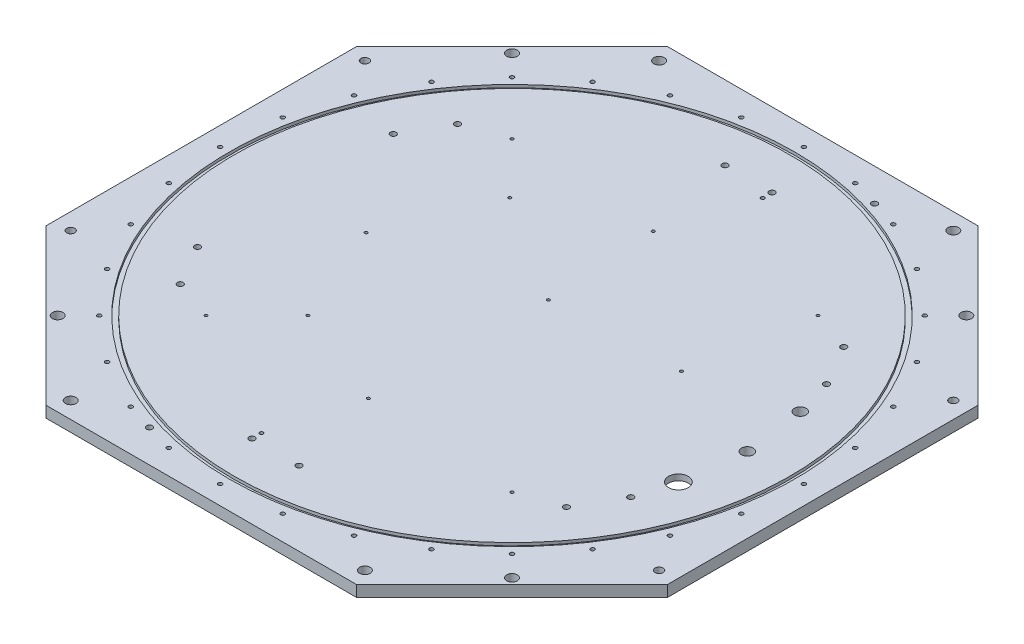
SolidWorks part; units mm, degrees
material "AISI 304"
ref_plane "Front" through (0, 0, 0) normal (0, 0, 1) x (1, 0, 0)
ref_plane "Top" through (0, 0, 0) normal (0, 1, 0) x (1, 0, 0)
ref_plane "Right" through (0, 0, 0) normal (1, 0, 0) x (0, 0, -1)
ref_axis "Axis1" through (0, -5.2388, 0) along (0, 1, 0)
sketch "Sketch1" plane through (0, 0, 0) normal (0, 1, 0) x (1, 0, 0)
  line L0 (-131.9798, 264) -> (131.9798, 264)
  line L1 (131.9798, 264) -> (264, 131.9798)
  line L2 (264, 131.9798) -> (264, -131.9798)
  line L3 (264, 0) -> (0, 0) construction
  line L4 (0, 0) -> (0, 264) construction
  line L5 (131.9798, -264) -> (264, -131.9798)
  line L6 (-131.9798, -264) -> (131.9798, -264)
  line L7 (-131.9798, -264) -> (-264, -131.9798)
  line L8 (-264, 131.9798) -> (-264, -131.9798)
  line L9 (-131.9798, 264) -> (-264, 131.9798)
  point P12 (0, -264)
  point P21 (0, 0)
  dimension "D1" = 528
  dimension "D2" = 280
extrude "Base Plate Profile" add sketch "Sketch1" along normal mid plane 9.525
hole_wizard "M3 Clearance Hole - For Cylinder" positions "Sketch2" profile "Sketch3" hole size "M3" standard "ANSI Metric" end condition up to next
sketch "Sketch2" plane through (0, 4.7625, 0) normal (0, 1, 0) x (1, 0, 0)
  line L0 (-248, 0) -> (248, 0) construction
  point P0 (248, 0)
  point P6 (243.2347, -48.3824)
  point P7 (229.1221, -94.9055)
  point P8 (206.2045, -137.7814)
  point P9 (175.3625, -175.3625)
  point P10 (137.7814, -206.2045)
  point P11 (94.9055, -229.1221)
  point P12 (48.3824, -243.2347)
  point P13 (0, -248)
  point P14 (-48.3824, -243.2347)
  point P15 (-94.9055, -229.1221)
  point P16 (-137.7814, -206.2045)
  point P17 (-175.3625, -175.3625)
  point P18 (-206.2045, -137.7814)
  point P19 (-229.1221, -94.9055)
  point P20 (-243.2347, -48.3824)
  point P21 (-248, 0)
  point P22 (-243.2347, 48.3824)
  point P23 (-229.1221, 94.9055)
  point P24 (-206.2045, 137.7814)
  point P25 (-175.3625, 175.3625)
  point P26 (-137.7814, 206.2045)
  point P27 (-94.9055, 229.1221)
  point P28 (-48.3824, 243.2347)
  point P29 (0, 248)
  point P30 (48.3824, 243.2347)
  point P31 (94.9055, 229.1221)
  point P32 (137.7814, 206.2045)
  point P33 (175.3625, 175.3625)
  point P34 (206.2045, 137.7814)
  point P35 (229.1221, 94.9055)
  point P36 (243.2347, 48.3824)
  dimension "D2" = 496
  dimension "D1" = 32
sketch "Sketch3" plane through (248, 4.7625, 0) normal (1, 0, 0) x (0, 0, 1)
  line L0 (0, 0) -> (0, 9.525)
  line L1 (0, 9.525) -> (1.7, 9.525)
  line L2 (1.7, 9.525) -> (1.7, 0)
  line L5 (1.7, 0) -> (0, 0)
  line L11 (0, -6.35) -> (0, 107.95) construction
  dimension "Thru Hole Dia." = 3.4
  dimension "Thru Hole Depth" = 9.525
hole_wizard "M6x1 Tapped Hole - For Support Pillars" positions "Sketch10" profile "Sketch11" tap size "M6x1.0" standard "ANSI Metric"
sketch "Sketch10" plane through (0, 4.7625, 0) normal (0, 1, 0) x (1, 0, 0)
  line L0 (-20, 201) -> (0, 201) construction
  line L1 (0, 201) -> (20, 201) construction
  line L6 (0, 0) -> (0, 201) construction
  line L7 (-20, -201) -> (20, -201) construction
  line L9 (0, -201) -> (0, 0) construction
  point P0 (-20, 201)
  point P2 (20, 201)
  point P39 (164.0711, 117.8205)
  point P40 (184.0711, 83.1795)
  point P41 (184.0711, -83.1795)
  point P42 (164.0711, -117.8205)
  point P43 (20, -201)
  point P44 (-20, -201)
  point P45 (-164.0711, -117.8205)
  point P46 (-184.0711, -83.1795)
  point P47 (-184.0711, 83.1795)
  point P48 (-164.0711, 117.8205)
  dimension "D1" = 40
  dimension "D2" = 6
  dimension "D3" = 201
cosmetic thread "Hole Thread1" parameters "D1"=6, "D2"=6
cosmetic thread "Hole Thread2" parameters "D1"=6, "D2"=6
cosmetic thread "Hole Thread3" parameters "D1"=6, "D2"=6
cosmetic thread "Hole Thread4" parameters "D1"=6, "D2"=6
cosmetic thread "Hole Thread5" parameters "D1"=6, "D2"=6
cosmetic thread "Hole Thread6" parameters "D1"=6, "D2"=6
cosmetic thread "Hole Thread7" parameters "D1"=6, "D2"=6
cosmetic thread "Hole Thread8" parameters "D1"=6, "D2"=6
cosmetic thread "Hole Thread9" parameters "D1"=6, "D2"=6
cosmetic thread "Hole Thread10" parameters "D1"=6, "D2"=6
cosmetic thread "Hole Thread11" parameters "D1"=6, "D2"=6
cosmetic thread "Hole Thread12" parameters "D1"=6, "D2"=6
sketch "Sketch11" plane through (-20, 4.7625, -201) normal (1, 0, 0) x (0, 0, 1)
  line L0 (0, 0) -> (0, 7.5022)
  line L1 (0, 7.5022) -> (2.5, 6)
  line L2 (2.5, 6) -> (2.5, 0)
  line L5 (2.5, 0) -> (0, 0)
  line L10 (0, 7.5022) -> (-2.5, 6) construction
  line L11 (0, -6.35) -> (0, 107.95) construction
  dimension "Tap Drill Dia." = 5
  dimension "Tap Drill Depth" = 6
  dimension "Drill Angle" = 118
hole_wizard "Ø3.0mm Dowel Hole - For Support Pillars" positions "Sketch12" profile "Sketch13" hole size "Ø3.0" standard "ANSI Metric"
sketch "Sketch12" plane through (0, 4.7625, 0) normal (0, 1, 0) x (1, 0, 0)
  line L1 (20, 193) -> (20, 201) construction
  line L3 (-20, -201) -> (-20, -193) construction
  point P0 (20, 193)
  point P2 (-20, -193)
  dimension "D1" = 8
sketch "Sketch13" plane through (20, 4.7625, -193) normal (1, 0, 0) x (0, 0, 1)
  line L0 (0, 0) -> (0, 6.9013)
  line L1 (0, 6.9013) -> (1.5, 6)
  line L2 (1.5, 6) -> (1.5, 0)
  line L5 (1.5, 0) -> (0, 0)
  line L10 (0, 6.9013) -> (-1.5, 6) construction
  line L11 (0, -6.35) -> (0, 107.95) construction
  dimension "Hole Dia." = 3
  dimension "Hole Depth" = 6
  dimension "Drill Angle" = 118
hole_wizard "M3x0.5 Tapped Hole - For PCB Standoffs" positions "Sketch14" profile "Sketch15" tap size "M3x0.5" standard "ANSI Metric"
sketch "Sketch14" plane through (0, 4.7625, 0) normal (0, 1, 0) x (1, 0, 0)
  line L13 (-150, -150) -> (150, -150) construction
  line L14 (-150, -150) -> (-150, 150) construction
  line L15 (-150, 150) -> (150, 150) construction
  line L16 (150, -150) -> (150, 150) construction
  line L17 (-150, -150) -> (150, 150) construction
  line L18 (-150, 150) -> (150, -150) construction
  point P133 (-130, -130)
  point P136 (130, -130)
  point P138 (130, 130)
  point P140 (-130, 130)
  point P143 (-86.8, -86.7)
  point P145 (0, -122)
  point P149 (-123, -1)
  point P152 (-87.7, 85.8)
  point P154 (4, 27)
  point P157 (-2, 122)
  point P159 (113, 31)
  dimension "D1" = 300
  dimension "D3" = 63.2
  dimension "D4" = 63.3
  dimension "D5" = 28
  dimension "D2" = 20
  dimension "D6" = 27
  dimension "D7" = 149
  dimension "D8" = 235.8
  dimension "D9" = 62.3
  dimension "D10" = 154
  dimension "D11" = 177
  dimension "D12" = 148
  dimension "D13" = 272
  dimension "D14" = 181
  dimension "D15" = 263
sketch "Sketch15" plane through (113, 4.7625, -31) normal (1, 0, 0) x (0, 0, 1)
  line L0 (0, 0) -> (0, 7.2511)
  line L1 (0, 7.2511) -> (1.25, 6.5)
  line L2 (1.25, 6.5) -> (1.25, 0)
  line L5 (1.25, 0) -> (0, 0)
  line L10 (0, 7.2511) -> (-1.25, 6.5) construction
  line L11 (0, -6.35) -> (0, 107.95) construction
  dimension "Tap Drill Dia." = 2.5
  dimension "Tap Drill Depth" = 6.5
  dimension "Drill Angle" = 118
cosmetic thread "Hole Thread13" parameters "D1"=5, "D2"=3
cosmetic thread "Hole Thread14" parameters "D1"=5, "D2"=3
cosmetic thread "Hole Thread15" parameters "D1"=5, "D2"=3
cosmetic thread "Hole Thread16" parameters "D1"=5, "D2"=3
cosmetic thread "Hole Thread17" parameters "D1"=5, "D2"=3
cosmetic thread "Hole Thread18" parameters "D1"=5, "D2"=3
cosmetic thread "Hole Thread19" parameters "D1"=5, "D2"=3
cosmetic thread "Hole Thread20" parameters "D1"=5, "D2"=3
cosmetic thread "Hole Thread21" parameters "D1"=5, "D2"=3
cosmetic thread "Hole Thread22" parameters "D1"=5, "D2"=3
cosmetic thread "Hole Thread23" parameters "D1"=5, "D2"=3
sketch "PCB Size Outline" plane through (0, -4.7625, 0) normal (0, -1, 0) x (1, 0, 0)
  line L1 (-150, -150) -> (150, -150)
  line L2 (-150, -150) -> (-150, 150)
  line L3 (-150, 150) -> (150, 150)
  line L4 (150, -150) -> (150, 150)
  line L5 (-150, -150) -> (150, 150) construction
  line L6 (-150, 150) -> (150, -150) construction
  point P0 (0, 0)
  dimension "D1" = 300
hole_wizard "M8 Clearance Hole - For Lifting / Alignment" positions "Sketch16" profile "Sketch17" hole size "M8" standard "ANSI Metric" end condition up to next
sketch "Sketch16" plane through (0, 4.7625, 0) normal (0, 1, 0) x (1, 0, 0)
  line L0 (-193.0402, 193.0402) -> (-193.0402, -193.0402) construction
  line L1 (-193.0402, -193.0402) -> (193.0402, -193.0402) construction
  line L2 (193.0402, -193.0402) -> (193.0402, 193.0402) construction
  line L3 (193.0402, 193.0402) -> (-193.0402, 193.0402) construction
  line L5 (-193.0402, 193.0402) -> (193.0402, -193.0402) construction
  point P0 (-193.0402, -193.0402)
  point P6 (-193.0402, 193.0402)
  point P7 (193.0402, 193.0402)
  point P8 (193.0402, -193.0402)
  dimension "D2" = 546
  dimension "D1" = 4
sketch "Sketch17" plane through (-193.0402, 4.7625, 193.0402) normal (1, 0, 0) x (0, 0, 1)
  line L0 (0, 0) -> (0, 9.525)
  line L1 (0, 9.525) -> (4.5, 9.525)
  line L2 (4.5, 9.525) -> (4.5, 0)
  line L5 (4.5, 0) -> (0, 0)
  line L11 (0, -6.35) -> (0, 107.95) construction
  dimension "Thru Hole Dia." = 9
  dimension "Thru Hole Depth" = 9.525
hole_wizard "M8x1.25 Tapped Hole -For Super Structure" positions "Sketch18" profile "Sketch19" tap size "M8x1.25" standard "ANSI Metric" end condition up to next
sketch "Sketch18" plane through (0, 4.7625, 0) normal (0, 1, 0) x (1, 0, 0)
  line L0 (-264, 0) -> (0, 0) construction
  line L1 (-264, 131.9798) -> (-264, -131.9798) construction
  line L2 (0, 0) -> (0, -264) construction
  line L3 (-131.9798, -264) -> (131.9798, -264) construction
  line L5 (0, 0) -> (-197.9899, -197.9899) construction
  line L6 (-264, -131.9798) -> (-131.9798, -264) construction
  point P22 (-250, -125)
  point P25 (-250, 125)
  point P27 (250, -125)
  point P28 (250, 125)
  dimension "D2" = 250
  dimension "D3" = 500
sketch "Sketch19" plane through (250, 4.7625, -125) normal (1, 0, 0) x (0, 0, 1)
  line L0 (0, 0) -> (0, 9.525)
  line L1 (0, 9.525) -> (3.4, 9.525)
  line L2 (3.4, 9.525) -> (3.4, 0)
  line L5 (3.4, 0) -> (0, 0)
  line L11 (0, -6.35) -> (0, 107.95) construction
  dimension "Thru Tap Drill Dia." = 6.8
  dimension "Thru Tap Drill Depth" = 9.525
cosmetic thread "Hole Thread34" parameters "D2"=8
cosmetic thread "Hole Thread35" parameters "D2"=8
cosmetic thread "Hole Thread37" parameters "D2"=8
cosmetic thread "Hole Thread39" parameters "D2"=8
hole_wizard "7/16-20 Tapped Hole - For Penetrator" positions "Sketch25" profile "Sketch26" tap size "7/16-20" standard "ANSI Inch" end condition up to next
sketch "Sketch25" plane through (0, -4.7625, 0) normal (0, -1, 0) x (-1, 0, 0)
  point P0 (-200, 0)
  dimension "D1" = 200
cosmetic thread "Hole Thread32" parameters "D2"=11.1125
sketch "Sketch26" plane through (200, -4.7625, 0) normal (1, 0, 0) x (0, 0, -1)
  line L0 (0, 0) -> (0, 9.525)
  line L1 (0, 9.525) -> (4.9606, 9.525)
  line L2 (4.9606, 9.525) -> (4.9606, 0)
  line L5 (4.9606, 0) -> (0, 0)
  line L11 (0, -6.35) -> (0, 107.95) construction
  dimension "Thru Tap Drill Dia." = 9.9212
  dimension "Thru Tap Drill Depth" = 9.525
sketch "Sketch28" plane through (0, 4.7625, 0) normal (0, 1, 0) x (1, 0, 0)
  line L0 (-150, -150) -> (150, 150) construction
  circle A0 centre (0, 0) radius 240.5
  circle A1 centre (0, 0) radius 236.3344
  dimension "D1" = 481
  dimension "D2" = 4.1656
extrude "O-ring Groove" cut sketch "Sketch28" against normal blind 2.413
sketch "Sketch_thickness" [suppressed] plane through (0, 0, 0) normal (1, 0, 0) x (0, 0, -1)
  line L0 (-88.2215, 4.7625) -> (-88.2215, -0.2425)
  line L1 (-131.9798, 4.7625) -> (131.9798, 4.7625) construction
  line L2 (-88.2215, -0.2425) -> (-88.2215, -4.7625)
  line L3 (-150, -4.7625) -> (150, -4.7625) construction
  dimension "D1" = 5.005
  dimension "D2" = 4.52
pattern_circular "CirPattern_extraCables" count 2 every 15 about axis through (0, -5.2388, 0) along (0, 1, 0) of "7/16-20 Tapped Hole - For Penetrator"
hole_wizard "5/8 Clearance Hole1" positions "Sketch32" profile "Sketch33" hole size "5/8" standard "ANSI Inch" end condition up to next
sketch "Sketch32" plane through (0, 4.7625, 0) normal (0, 1, 0) x (1, 0, 0)
  line L0 (0, 0) -> (193.1852, -51.7638) construction
  line L2 (0, 0) -> (200, 0) construction
  point P0 (193.1852, -51.7638)
  dimension "D1" = 200
  dimension "D2" = 15
sketch "Sketch33" plane through (193.1852, 4.7625, 51.7638) normal (1, 0, 0) x (0, 0, 1)
  line L0 (0, 0) -> (0, 9.525)
  line L1 (0, 9.525) -> (8.3337, 9.525)
  line L2 (8.3337, 9.525) -> (8.3337, 0)
  line L5 (8.3337, 0) -> (0, 0)
  line L11 (0, -6.35) -> (0, 107.95) construction
  dimension "Thru Hole Dia." = 16.6675
  dimension "Thru Hole Depth" = 9.525
sketch "Sketch35" plane through (0, -4.7625, 0) normal (0, -1, 0) x (1, 0, 0)
  circle A0 centre (193.1852, 51.7638) radius 18
  dimension "D1" = 36
extrude "Cut-Extrude1" cut sketch "Sketch35" against normal blind 4.5
hole_wizard "M8 Clearance Hole" positions "Sketch37" profile "Sketch39" hole size "M8" standard "ANSI Metric" end condition up to next
sketch "Sketch37" plane through (-28.1239, 4.7625, -48.0675) normal (0, 1, 0) x (1, 0, 0)
  line L0 (-235.8761, -48.0675) -> (28.1239, -48.0675) construction
  line L2 (28.1239, -48.0675) -> (28.1239, -312.0675) construction
  line L5 (28.1239, -48.0675) -> (-169.866, -246.0574) construction
  line L7 (-103.8559, -312.0675) -> (160.1037, -312.0675) construction
  line L8 (-235.8761, 83.9123) -> (-235.8761, -180.0473) construction
  line L9 (-235.8761, -180.0473) -> (-103.8559, -312.0675) construction
  point P0 (-96.8761, -298.0675)
  point P24 (-96.8761, 201.9325)
  point P26 (153.1239, -298.0675)
  point P29 (153.1239, 201.9325)
  dimension "D1" = 250
  dimension "D2" = 500
sketch "Sketch39" plane through (-125, 4.7625, 250) normal (1, 0, 0) x (0, 0, 1)
  line L0 (0, 0) -> (0, 9.525)
  line L1 (0, 9.525) -> (4.5, 9.525)
  line L2 (4.5, 9.525) -> (4.5, 0)
  line L5 (4.5, 0) -> (0, 0)
  line L11 (0, -6.35) -> (0, 107.95) construction
  dimension "Thru Hole Dia." = 9
  dimension "Thru Hole Depth" = 9.525
hole_wizard "Ø5.0mm Dowel Hole1" positions "Sketch42" profile "Sketch43" hole size "Ø5.0" standard "ANSI Metric"
sketch "Sketch42" plane through (0, 4.7625, 0) normal (0, 1, 0) x (1, 0, 0)
  point P0 (71.7003, 236.3643)
  point P3 (-71.7003, -236.3643)
sketch "Sketch43" plane through (71.7003, 4.7625, -236.3643) normal (1, 0, 0) x (0, 0, 1)
  line L0 (0, 0) -> (0, 6.5172)
  line L1 (0, 6.5172) -> (2.525, 5)
  line L2 (2.525, 5) -> (2.525, 0)
  line L5 (2.525, 0) -> (0, 0)
  line L10 (0, 6.5172) -> (-2.525, 5) construction
  line L11 (0, -6.35) -> (0, 107.95) construction
  dimension "Hole Dia." = 5.05
  dimension "Hole Depth" = 5
  dimension "Drill Angle" = 118
sketch "Sketch44" plane through (0, 0, 0) normal (0, 0, 1) x (1, 0, 0)
  line L0 (0, 0) -> (0, 113.0488) construction
